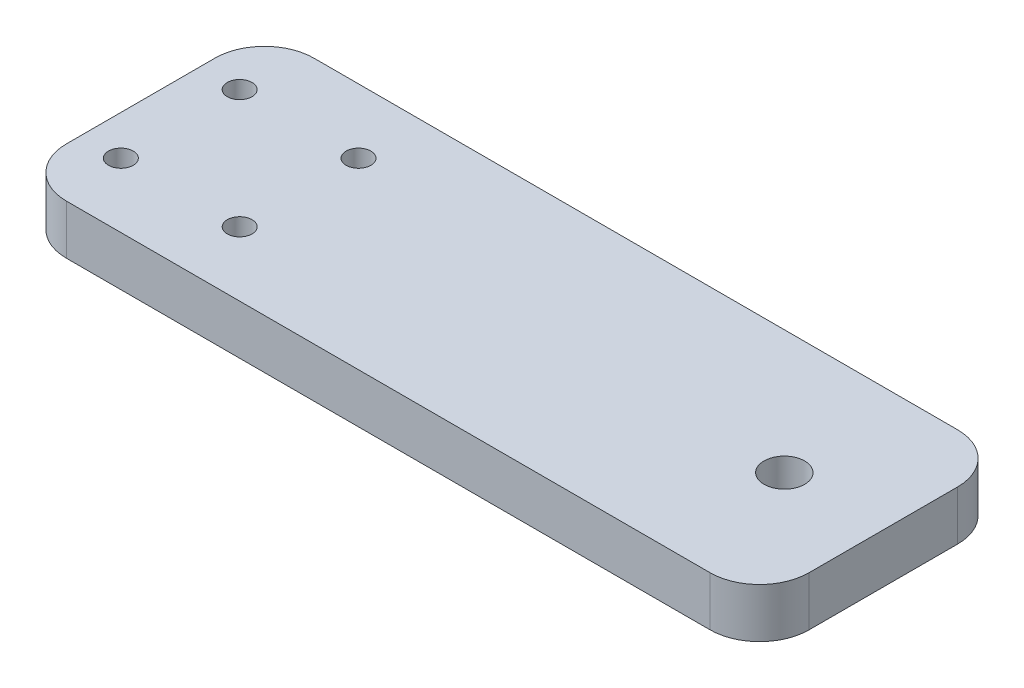
SolidWorks part; units mm, degrees
ref_plane "正面" through (0, 0, 0) normal (0, 0, 1) x (1, 0, 0)
ref_plane "平面" through (0, 0, 0) normal (0, 1, 0) x (1, 0, 0)
ref_plane "右側面" through (0, 0, 0) normal (1, 0, 0) x (0, 0, -1)
sketch "ｽｹｯﾁ1" plane through (0, 0, 0) normal (0, 1, 0) x (1, 0, 0)
  line L1 (-75, -25) -> (75, -25)
  line L2 (-75, -25) -> (-75, 25)
  line L3 (-75, 25) -> (75, 25)
  line L4 (75, -25) -> (75, 25)
  line L5 (-75, -25) -> (75, 25) construction
  line L6 (-75, 25) -> (75, -25) construction
  point P0 (0, 0)
  dimension "D1" = 50
  dimension "D2" = 150
extrude "ﾎﾞｽ - 押し出し1" add sketch "ｽｹｯﾁ1" along normal blind 10
fillet "ﾌｨﾚｯﾄ1" radius 10 4 edges at (-75, 5, -25) (75, 5, -25) (75, 5, 25) (-75, 5, 25)
sketch "ｽｹｯﾁ2" plane through (0, 10, 0) normal (0, 1, 0) x (1, 0, 0)
  line L0 (-55, 0) -> (55, 0) construction
  line L1 (-75, 15) -> (-75, -15) construction
  circle A0 centre (-67, 12) radius 2.5
  circle A1 centre (-43, 12) radius 2.5
  circle A2 centre (-67, -12) radius 2.5
  circle A3 centre (-43, -12) radius 2.5
  circle A4 centre (55, 0) radius 4.1
  dimension "D3" = 5
  dimension "D8" = 8.2
  dimension "D1" = 110
  dimension "D2" = 20
  dimension "D4" = 24
  dimension "D5" = 24
  dimension "D6" = 12
  dimension "D7" = 12
extrude "ｶｯﾄ - 押し出し1" cut sketch "ｽｹｯﾁ2" against normal through all
